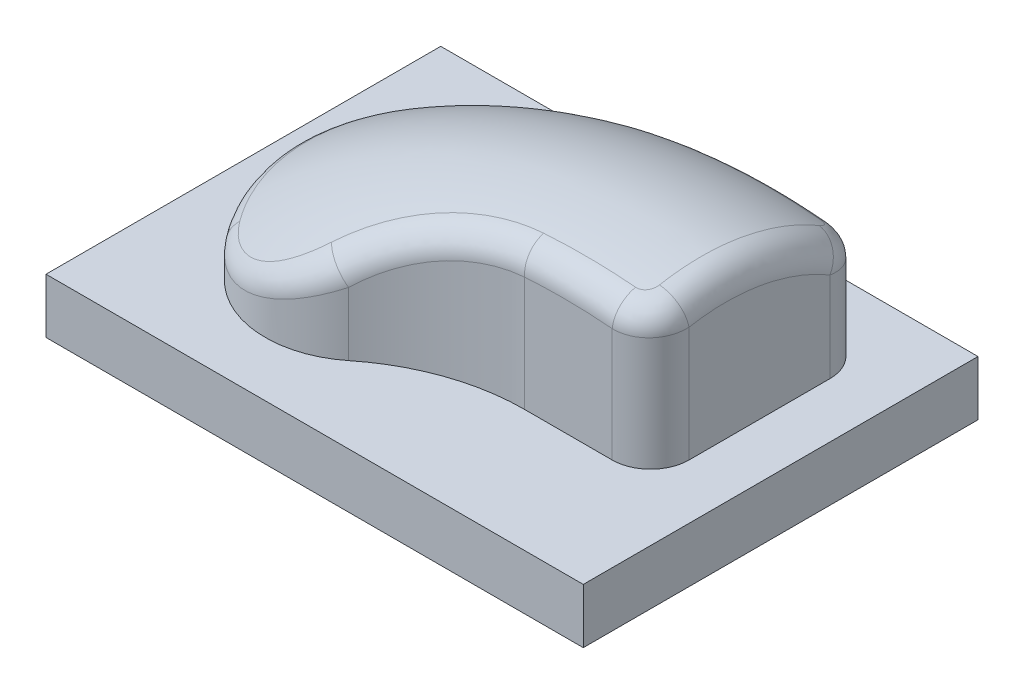
SolidWorks part; units mm, degrees
ref_plane "정면" through (0, 0, 0) normal (0, 0, 1) x (1, 0, 0)
ref_plane "윗면" through (0, 0, 0) normal (0, 1, 0) x (1, 0, 0)
ref_plane "우측면" through (0, 0, 0) normal (1, 0, 0) x (0, 0, -1)
sketch "스케치1" plane through (0, 0, 0) normal (0, 1, 0) x (1, 0, 0)
  line L1 (-49, 36) -> (49, 36)
  line L2 (-49, 36) -> (-49, -36)
  line L3 (-49, -36) -> (49, -36)
  line L4 (49, 36) -> (49, -36)
  line L5 (-49, 36) -> (49, -36) construction
  line L6 (-49, -36) -> (49, 36) construction
  point P0 (0, 0)
  dimension "D1" = 98
  dimension "D2" = 72
extrude "보스-돌출1" add sketch "스케치1" along normal blind 10
sketch "스케치2" plane through (0, 10, 0) normal (0, 1, 0) x (1, 0, 0)
  line L0 (-11, 26) -> (32, 26)
  line L1 (16, -13.715) -> (32, -13.715)
  line L2 (39, 19) -> (39, -6.715)
  line L3 (49, -36) -> (49, 36) construction
  line L4 (-39, 47.1116) -> (-39, -52.709) construction
  line L5 (-67.0135, -26) -> (67.9464, -26) construction
  line L6 (-49, -36) -> (49, -36) construction
  line L7 (49, 36) -> (-49, 36) construction
  arc A0 (-11, 26) -> (-33.4, -18.8) centre (-11, -2) ccw
  arc A1 (-7.75, -22.0512) -> (-33.4, -18.8) centre (-19, -8) cw
  arc A2 (-7.75, -22.0512) -> (16, -13.715) centre (16, -51.715) cw
  arc A3 (39, 19) -> (32, 26) centre (32, 19) ccw
  arc A4 (39, -6.715) -> (32, -13.715) centre (32, -6.715) cw
  dimension "D1" = 18
  dimension "D2" = 28
  dimension "D5" = 7
  dimension "D7" = 38
  dimension "D10" = 7
  dimension "D3" = 10
  dimension "D4" = 39
  dimension "D6" = 23
  dimension "D8" = 10
  dimension "D9" = 10
extrude "보스-돌출2" add sketch "스케치2" along normal blind 36
sketch "스케치6" plane through (0, 0, 0) normal (0, 0, 1) x (1, 0, 0)
  line L1 (39, 46) -> (39, 10) construction
  line L2 (-49, 0) -> (49, 0) construction
  line L5 (-39, 46) -> (-39, 10) construction
  arc A0 (-40, 17.3089) -> (40, 35.8486) centre (23.039, -72.8359) cw
  point P3 (0, 0)
  point P6 (39, 36)
  point P8 (-39, 18)
  dimension "D2" = 110
  dimension "D1" = 18
  dimension "D3" = 36
  dimension "D4" = 40
  dimension "D5" = 40
sketch "스케치7" plane through (39, 0, 0) normal (1, 0, 0) x (0, 0, -1)
  line L0 (26, 46) -> (26, 10) construction
  line L1 (-26, 46) -> (-26, 10) construction
  line L3 (-26, 26.9848) -> (-29.7553, 41)
  line L4 (-29.7553, 41) -> (29.7553, 41)
  line L5 (29.7553, 41) -> (26, 26.9848)
  line L6 (-36, 10) -> (36, 10) construction
  line L7 (0, 37.1641) -> (0, 17.3089) construction
  line L8 (-36, 0) -> (36, 0) construction
  arc A0 (-26, 26.9848) -> (26, 26.9848) centre (0, -6) cw
  point P10 (0, 36)
  point P12 (0, 0)
  point P17 (0, 0)
  dimension "D1" = 42
  dimension "D2" = 15
  dimension "D3" = 5
  dimension "D4" = 75
  dimension "D5" = 36
sweep "컷-스윕5" cut profiles "스케치7" path "스케치6"
fillet "필렛1" radius 5 8 edges at (36.2449, 34.5392, 12.2811) (24.0027, 34.8823, 13.715) (1.1149, 31.437, 16.7517) (-19.9051, 18.6972, 25.9772) (-33.7734, 18.4503, -14.2903) (10.2014, 27.4344, -26) (37.064, 28.869, -23.8327) (39, 35.3453, -7.3869)
